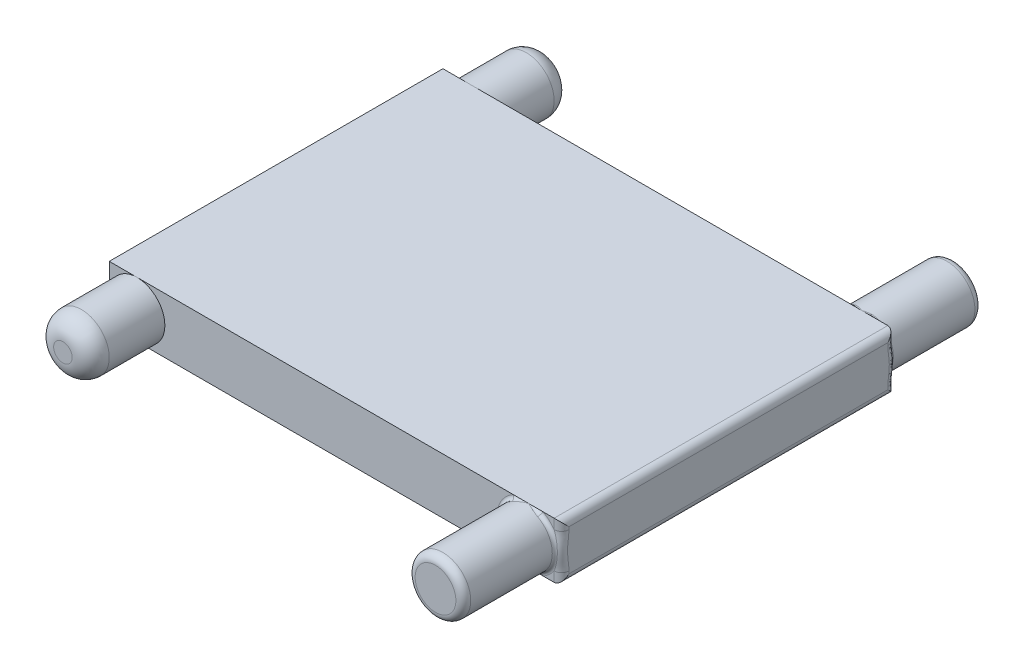
SolidWorks part; units mm, degrees
ref_plane "Front Plane" through (0, 0, 0) normal (0, 0, 1) x (1, 0, 0)
ref_plane "Top Plane" through (0, 0, 0) normal (0, 1, 0) x (1, 0, 0)
ref_plane "Right Plane" through (0, 0, 0) normal (1, 0, 0) x (0, 0, -1)
sketch "Sketch1" plane through (0, 0, 0) normal (0, 1, 0) x (1, 0, 0)
  line L1 (0, 0) -> (12.2, 0)
  line L2 (0, 0) -> (0, 9)
  line L3 (0, 9) -> (12.2, 9)
  line L4 (12.2, 0) -> (12.2, 9)
  dimension "D1" = 12.2
  dimension "D2" = 9
extrude "Boss-Extrude1" add sketch "Sketch1" along normal blind 1.5
sketch "Sketch2" plane through (0, 0, 0) normal (0, 0, 1) x (1, 0, 0)
  line L0 (0, 1.5) -> (0, 0) construction
  line L1 (0, 0) -> (12.2, 0) construction
  circle A0 centre (0.75, 0.75) radius 0.75
  dimension "D1" = 1.5
  dimension "D2" = 0.75
  dimension "D3" = 0.75
extrude "Boss-Extrude2" add sketch "Sketch2" along normal blind 2 and the other way blind 11 contours A0
fillet "Fillet1" radius 0.5 1 edges at (1.5, 0.75, 2)
fillet "Fillet3" radius 0.5 1 edges at (1.5, 0.75, -11)
sketch "Sketch3" plane through (0, 0, 0) normal (0, 0, 1) x (1, 0, 0)
  line L0 (0.75, 0) -> (12.2, 0) construction
  line L1 (12.2, 1.5) -> (12.2, 0) construction
  circle A0 centre (11.3, 0.75) radius 0.75
  dimension "D1" = 1.5
  dimension "D2" = 0.75
  dimension "D3" = 0.9
extrude "Boss-Extrude3" add sketch "Sketch3" along normal blind 2.5 and the other way blind 11.5
fillet "Fillet4" radius 0.1 2 edges at (12.05, 0.75, 0) (10.55, 0.75, 0)
fillet "Fillet5" radius 0.1 2 edges at (10.55, 0.75, -9) (12.05, 0.75, -9)
fillet "Fillet6" radius 0.2 2 edges at (12.05, 0.75, -11.5) (12.05, 0.75, 2.5)
fillet "Fillet7" radius 0.2 4 edges at (12.2, 0.75, 0) (12.2, 1.5, -4.5) (12.2, 0.75, -9) (12.2, 0, -4.5)
